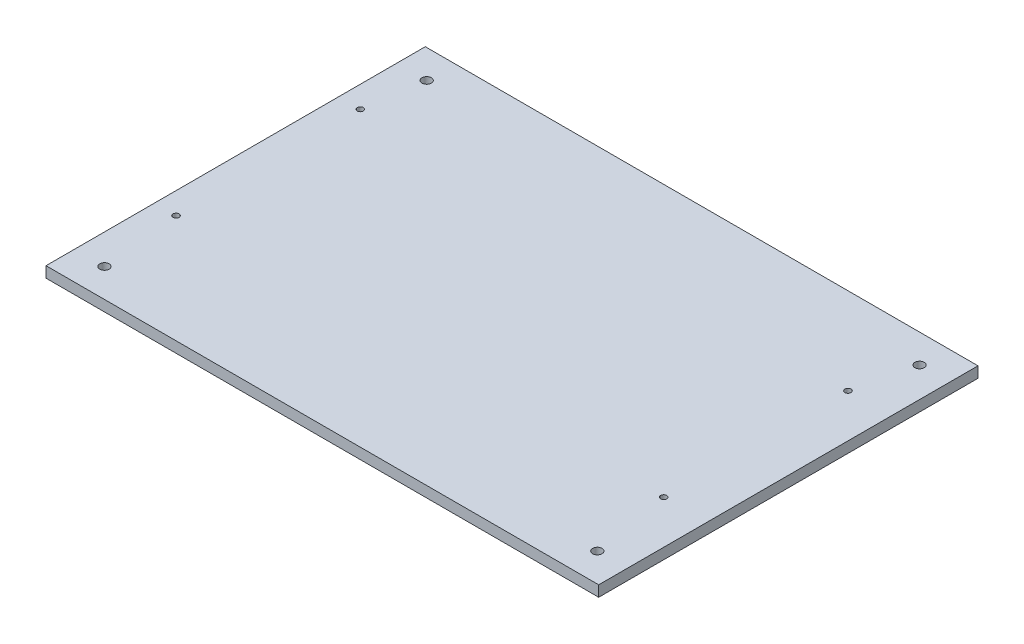
SolidWorks part; units mm, degrees
material "Pine"
ref_plane "Front Plane" through (0, 0, 0) normal (0, 0, 1) x (1, 0, 0)
ref_plane "Top Plane" through (0, 0, 0) normal (0, 1, 0) x (1, 0, 0)
ref_plane "Right Plane" through (0, 0, 0) normal (1, 0, 0) x (0, 0, -1)
ref_axis "X AXIS" through (-88.99, 0, 0) along (1, 0, 0)
ref_axis "Y AXIS" through (0, -55, 0) along (0, 1, 0)
ref_axis "Z AXIS" through (0, 0, 55) along (0, 0, -1)
other "Freeze***"
sketch "Sketch1" plane through (0, 0, 0) normal (0, 1, 0) x (1, 0, 0)
  line L1 (-161.925, -111.125) -> (161.925, -111.125)
  line L2 (-161.925, -111.125) -> (-161.925, 111.125)
  line L3 (-161.925, 111.125) -> (161.925, 111.125)
  line L4 (161.925, -111.125) -> (161.925, 111.125)
  line L5 (0, 111.125) -> (0, -111.125) construction
  line L6 (-161.925, 0) -> (161.925, 0) construction
  point P0 (0, 0)
  dimension "D1" = 323.85
  dimension "D2" = 222.25
extrude "Boss-Extrude1" add sketch "Sketch1" along normal mid plane 6.35
hole_wizard "M5 Clearance Hole1" positions "Sketch2" profile "Sketch3" hole size "M5" standard "ANSI Metric" end condition through all
sketch "Sketch2" plane through (0, 3.175, 0) normal (0, 1, 0) x (1, 0, 0)
  line L0 (-161.925, 0) -> (0, 0) construction
  line L1 (-161.925, 111.125) -> (-161.925, -111.125) construction
  line L2 (0, 0) -> (0, 111.125) construction
  line L3 (161.925, 111.125) -> (-161.925, 111.125) construction
  point P0 (-144.399, 94.3991)
  point P13 (144.399, 94.3991)
  point P14 (144.399, -94.3991)
  point P15 (-144.399, -94.3991)
  dimension "D1" = 188.7982
  dimension "D2" = 288.798
sketch "Sketch3" plane through (-144.399, 3.175, -94.3991) normal (1, 0, 0) x (0, 0, 1)
  line L0 (0, 0) -> (0, 6.35)
  line L1 (0, 6.35) -> (2.75, 6.35)
  line L2 (2.75, 6.35) -> (2.75, 0)
  line L5 (2.75, 0) -> (0, 0)
  line L11 (0, -6.35) -> (0, 107.95) construction
  dimension "Thru Hole Dia." = 5.5
  dimension "Thru Hole Depth" = 6.35
hole_wizard "9/64 (0.14063) Diameter Hole1" positions "Sketch4" profile "Sketch5" hole size "9/64" standard "ANSI Inch" end condition through all
sketch "Sketch4" plane through (0, 3.175, 0) normal (0, 1, 0) x (1, 0, 0)
  line L1 (-149.225, 60.325) -> (136.525, 60.325)
  line L2 (-149.225, 60.325) -> (-149.225, -47.625)
  line L3 (-149.225, -47.625) -> (136.525, -47.625)
  line L4 (136.525, 60.325) -> (136.525, -47.625)
  line L5 (-161.925, 111.125) -> (-161.925, -111.125) construction
  line L6 (161.925, 111.125) -> (-161.925, 111.125) construction
  point P1 (-149.225, 60.325)
  point P47 (-149.225, -47.625)
  point P48 (136.525, 60.325)
  point P56 (136.525, -47.625)
  point P58 (68.8195, -26.6181)
  point P59 (141.0452, 67.2244)
  dimension "D1" = 285.75
  dimension "D2" = 107.95
  dimension "D3" = 12.7
  dimension "D4" = 50.8
sketch "Sketch5" plane through (-149.225, 3.175, -60.325) normal (1, 0, 0) x (0, 0, 1)
  line L0 (0, 0) -> (0, 6.35)
  line L1 (0, 6.35) -> (1.786, 6.35)
  line L2 (1.786, 6.35) -> (1.786, 0)
  line L5 (1.786, 0) -> (0, 0)
  line L11 (0, -6.35) -> (0, 107.95) construction
  dimension "Thru Hole Dia." = 3.572
  dimension "Thru Hole Depth" = 6.35
